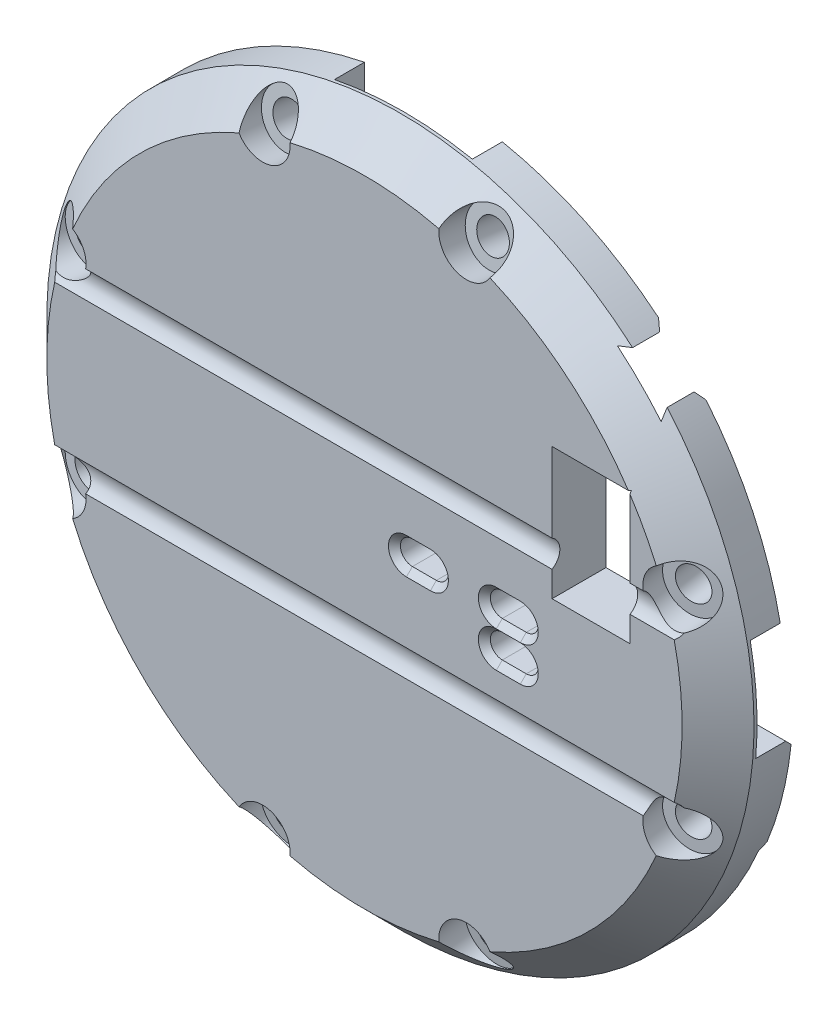
SolidWorks part; units mm, degrees
ref_plane "Front Plane" through (0, 0, 0) normal (0, 0, 1) x (1, 0, 0)
ref_plane "Top Plane" through (0, 0, 0) normal (0, 1, 0) x (1, 0, 0)
ref_plane "Right Plane" through (0, 0, 0) normal (1, 0, 0) x (0, 0, -1)
sketch "Sketch1" plane through (0, 0, 0) normal (0, 0, 1) x (1, 0, 0)
  circle A0 centre (0, 0) radius 29.5
  dimension "D1" = 59
extrude "Boss-Extrude1" add sketch "Sketch1" along normal blind 5.75
sketch "Sketch3" plane through (0, 0, 0) normal (0, 0, -1) x (-1, 0, 0)
  line L1 (-22.25, -22.25) -> (22.25, -22.25)
  line L2 (-22.25, -22.25) -> (-22.25, 22.25)
  line L3 (-22.25, 22.25) -> (22.25, 22.25)
  line L4 (22.25, -22.25) -> (22.25, 22.25)
  line L5 (-22.25, -22.25) -> (22.25, 22.25) construction
  line L6 (-22.25, 22.25) -> (22.25, -22.25) construction
  point P0 (0, 0)
  dimension "D1" = 44.5
extrude "Cut-Extrude1" cut sketch "Sketch3" against normal blind 3.25
sketch "Sketch26" plane through (0, 0, 0) normal (0, 0, -1) x (-1, 0, 0)
  line L1 (22.25, 19.3698) -> (22.25, 17.8098)
  line L2 (19.3698, -22.25) -> (17.8098, -22.25)
  line L3 (-22.25, -19.3698) -> (-22.25, -17.8098)
  line L4 (17.8098, 22.25) -> (19.3698, 22.25)
  line L6 (22.25, -17.8098) -> (22.25, -19.3698)
  line L7 (-17.8098, -22.25) -> (-19.3698, -22.25)
  arc A4 (-22.25, -19.3698) -> (-19.3698, -22.25) centre (0, 0) ccw
  arc A5 (-22.25, -17.8098) -> (-17.8098, -22.25) centre (0, 0) ccw
  arc A6 (22.25, 17.8098) -> (17.8098, 22.25) centre (0, 0) ccw
  arc A7 (22.25, 19.3698) -> (19.3698, 22.25) centre (0, 0) ccw
  arc A8 (17.8098, -22.25) -> (22.25, -17.8098) centre (0, 0) ccw
  arc A9 (19.3698, -22.25) -> (22.25, -19.3698) centre (0, 0) ccw
  dimension "D1" = 1
extrude "Boss-Extrude5" add sketch "Sketch26" against normal up to surface (3.25 mm away) up to face at (0, 0, 3.25)
chamfer "Chamfer2" distance 3 angle 45 1 edges at (29.5, 0, 5.75)
sketch "Sketch9" plane through (0, 0, 0) normal (1, 0, 0) x (0, 0, -1)
  line L0 (-26.5723, 0) -> (15.7273, 0) construction
  line L3 (-5.75, 26.5) -> (-5.75, -26.5) construction
  circle A0 centre (-6.4, 7) radius 1.3
  circle A1 centre (-6.4, -7) radius 1.3
  dimension "D1" = 2.6
  dimension "D2" = 14
  dimension "D3" = 0.65
extrude "Cut-Extrude5" cut sketch "Sketch9" against normal through all both and the other way through all
sketch "Sketch10" plane through (0, 0, 0) normal (0, 0, -1) x (-1, 0, 0)
  line L1 (22.0007, 5.75) -> (34.0342, 5.75)
  line L2 (22.0007, 5.75) -> (22.0007, -5.75)
  line L3 (22.0007, -5.75) -> (34.0342, -5.75)
  line L4 (34.0342, 5.75) -> (34.0342, -5.75)
  line L8 (-22.0007, -5.75) -> (-34.0342, -5.75)
  line L9 (-22.0007, -5.75) -> (-22.0007, 5.75)
  line L10 (-22.0007, 5.75) -> (-34.0342, 5.75)
  line L11 (-34.0342, -5.75) -> (-34.0342, 5.75)
  line L12 (-5.75, 22.0007) -> (-5.75, 34.0342)
  line L13 (-5.75, 22.0007) -> (5.75, 22.0007)
  line L14 (5.75, 22.0007) -> (5.75, 34.0342)
  line L15 (-5.75, 34.0342) -> (5.75, 34.0342)
  line L16 (5.75, -22.0007) -> (5.75, -34.0342) [skipped]
  line L17 (5.75, -22.0007) -> (-5.75, -22.0007) [skipped]
  line L18 (-5.75, -22.0007) -> (-5.75, -34.0342) [skipped]
  line L19 (5.75, -34.0342) -> (-5.75, -34.0342) [skipped]
  point P4 (22.0007, 0)
  point P21 (0, 0)
  dimension "D1" = 11.5
  dimension "D2" = 4
extrude "Cut-Extrude6" cut sketch "Sketch10" against normal blind 2.5
sketch "Sketch13" plane through (0, 0, 3.25) normal (0, 0, -1) x (-1, 0, 0)
  line L0 (-22.25, 18.5994) -> (-22.25, -17.8098) construction
  line L1 (-22.15, 14.75) -> (-15.65, 14.75)
  line L2 (-22.15, 14.75) -> (-22.15, 3.75)
  line L3 (-22.15, 3.75) -> (-15.65, 3.75)
  line L4 (-15.65, 14.75) -> (-15.65, 3.75)
  line L5 (17.8098, 22.25) -> (-18.5994, 22.25) construction
  point P23 (0, 0)
  dimension "D1" = 0.1
  dimension "D2" = 7.5
  dimension "D4" = 11
  dimension "D3" = 6.5
extrude "Cut-Extrude9" cut sketch "Sketch13" against normal through all
sketch "Sketch14" plane through (0, 0, 0) normal (0, 0, -1) x (-1, 0, 0)
  line L1 (-35.1198, 0) -> (-19.2322, 0)
  line L2 (-35.1198, 0) -> (-35.1198, -11.6)
  line L3 (-35.1198, -11.6) -> (-19.2322, -11.6)
  line L4 (-19.2322, 0) -> (-19.2322, -11.6)
  dimension "D1" = 11.6
extrude "Cut-Extrude10" cut sketch "Sketch14" against normal up to surface (2.5 mm away) up to face at (25.7335, 0, 2.5)
sketch "Sketch15" plane through (0, 0, 5.75) normal (0, 0, 1) x (1, 0, 0)
  line L0 (0, 0) -> (12.0208, 12.0208) construction
  line L1 (0, 0) -> (36.7921, 0) construction
  circle A0 centre (12.0208, 12.0208) radius 12.5
  circle A1 centre (0, 0) radius 29.5 construction
  dimension "D2" = 25
  dimension "D1" = 45
ref_axis "Axis1" through (0, 0, -0.2945) along (0, 0, 1)
ref_axis "Axis2" through (0, 31.9, 0) along (0, -1, 0)
ref_plane "Plane1" through (0, 0, 0) normal (0.1392, 0, 0.9903) x (0, -1, 0)
sketch "Sketch23" plane through (0, 0, 2.5) normal (0, 0, -1) x (-1, 0, 0)
  line L0 (-22.25, -2.55) -> (-29.3896, -2.55)
  line L1 (-22.25, -2.55) -> (-22.25, -11.6)
  line L2 (-22.25, -11.6) -> (-27.1236, -11.6)
  line L3 (-22.25, 5.75) -> (-28.9342, 5.75) construction
  arc A0 (-29.3896, -2.55) -> (-27.1236, -11.6) centre (0, 0) ccw
  arc A1 (-28.9342, 5.75) -> (-27.1236, -11.6) centre (0, 0) ccw construction
  dimension "D1" = 8.3
extrude "Boss-Extrude3" add sketch "Sketch23" along normal blind 3
sketch "Sketch17" plane through (0, 0, 0) normal (0.1392, 0, 0.9903) x (0, -1, 0)
  line L0 (0, 0) -> (0, 33.2124) construction
  line L1 (0, 0.041) -> (0, -0.8607) construction
  circle A0 centre (-8.5, 24.5) radius 1.35
  circle A1 centre (8.5, 24.5) radius 1.35
  dimension "D1" = 2.7
  dimension "D2" = 17
  dimension "D3" = 24.5
extrude "Cut-Extrude12" cut sketch "Sketch17" along normal through all
sketch "Sketch18" plane through (0, 0, 0) normal (0.1392, 0, 0.9903) x (0, -1, 0)
  circle A0 centre (-8.5, 24.5) radius 2.3
  circle A1 centre (8.5, 24.5) radius 2.3
  dimension "D1" = 4.6
extrude "Cut-Extrude13" cut sketch "Sketch18" against normal blind 13 from offset 20
pattern_circular "CirPattern1" count 4 over 360 about axis through (0, 0, -0.2945) along (0, 0, 1) of "Cut-Extrude12", "Cut-Extrude13"
sketch "Sketch19" plane through (0, 0, 5.75) normal (0, 0, 1) x (1, 0, 0)
  line L0 (3.5, 0.75) -> (5.5, 0.75) construction
  line L1 (3.5, 1.75) -> (5.5, 1.75)
  line L2 (3.5, -0.25) -> (5.5, -0.25)
  line L3 (11, 0.75) -> (13, 0.75) construction
  line L4 (11, 1.75) -> (13, 1.75)
  line L5 (11, -0.25) -> (13, -0.25)
  line L6 (11, -2.25) -> (13, -2.25) construction
  line L7 (11, -1.25) -> (13, -1.25)
  line L8 (11, -3.25) -> (13, -3.25)
  arc A0 (3.5, 1.75) -> (3.5, -0.25) centre (3.5, 0.75) ccw
  arc A1 (5.5, -0.25) -> (5.5, 1.75) centre (5.5, 0.75) ccw
  arc A2 (11, 1.75) -> (11, -0.25) centre (11, 0.75) ccw
  arc A3 (13, -0.25) -> (13, 1.75) centre (13, 0.75) ccw
  arc A4 (11, -1.25) -> (11, -3.25) centre (11, -2.25) ccw
  arc A5 (13, -3.25) -> (13, -1.25) centre (13, -2.25) ccw
  point P2 (4.5, 0.75)
  point P8 (12, 0.75)
  point P16 (12, -2.25)
  dimension "D1" = 1
  dimension "D2" = 3
  dimension "D3" = 7.5
  dimension "D4" = 4.5
  dimension "D5" = 2
  dimension "D6" = 0.75
extrude "Cut-Extrude14" cut sketch "Sketch19" against normal through all
sketch "Sketch21" plane through (0, 0, 3.25) normal (0, 0, -1) x (-1, 0, 0)
  line L61 (-5.5, -0.35) -> (-3.5, -0.35)
  line L62 (-3.5, 1.85) -> (-5.5, 1.85)
  line L63 (-5.5, -0.35) -> (-3.5, -0.35)
  line L64 (-3.5, 1.85) -> (-5.5, 1.85)
  line L69 (-11, 1.85) -> (-13, 1.85)
  line L70 (-13, -0.35) -> (-11, -0.35)
  line L71 (-11, 1.85) -> (-13, 1.85)
  line L72 (-13, -0.35) -> (-11, -0.35)
  line L75 (-5.5, -1.35) -> (-3.5, -1.35)
  line L76 (-3.5, 2.85) -> (-5.5, 2.85)
  line L77 (-11, -1.15) -> (-13, -1.15)
  line L78 (-13, -3.35) -> (-11, -3.35)
  line L79 (-11, -1.15) -> (-13, -1.15)
  line L80 (-13, -3.35) -> (-11, -3.35)
  line L81 (-11, 2.85) -> (-13, 2.85)
  line L84 (-13, -4.35) -> (-11, -4.35)
  line L85 (-13, -1.35) -> (-11, -1.35) construction
  line L86 (-11, -0.15) -> (-13, -0.15) construction
  arc A55 (-5.5, 1.85) -> (-5.5, -0.35) centre (-5.5, 0.75) ccw
  arc A56 (-3.5, -0.35) -> (-3.5, 1.85) centre (-3.5, 0.75) ccw
  arc A57 (-5.5, 1.85) -> (-5.5, -0.35) centre (-5.5, 0.75) ccw
  arc A58 (-3.5, -0.35) -> (-3.5, 1.85) centre (-3.5, 0.75) ccw
  arc A65 (-13, 1.85) -> (-13, -0.35) centre (-13, 0.75) ccw
  arc A66 (-11, -0.35) -> (-11, 1.85) centre (-11, 0.75) ccw
  arc A67 (-13, 1.85) -> (-13, -0.35) centre (-13, 0.75) ccw
  arc A68 (-11, -0.35) -> (-11, 1.85) centre (-11, 0.75) ccw
  arc A73 (-5.5, 2.85) -> (-5.5, -1.35) centre (-5.5, 0.75) ccw
  arc A74 (-3.5, -1.35) -> (-3.5, 2.85) centre (-3.5, 0.75) ccw
  arc A75 (-13, -1.15) -> (-13, -3.35) centre (-13, -2.25) ccw
  arc A76 (-11, -3.35) -> (-11, -1.15) centre (-11, -2.25) ccw
  arc A77 (-13, -1.15) -> (-13, -3.35) centre (-13, -2.25) ccw
  arc A78 (-11, -3.35) -> (-11, -1.15) centre (-11, -2.25) ccw
  arc A80 (-13, 2.85) -> (-14.4697, -0.75) centre (-13, 0.75) ccw
  arc A81 (-11, -4.35) -> (-9.5303, -0.75) centre (-11, -2.25) ccw
  arc A84 (-9.5303, -0.75) -> (-11, 2.85) centre (-11, 0.75) ccw
  arc A85 (-11, -4.35) -> (-11, -0.15) centre (-11, -2.25) ccw construction
  arc A86 (-14.4697, -0.75) -> (-13, -4.35) centre (-13, -2.25) ccw
  arc A87 (-11, -1.35) -> (-11, 2.85) centre (-11, 0.75) ccw construction
  arc A88 (-13, 2.85) -> (-13, -1.35) centre (-13, 0.75) ccw construction
  arc A90 (-13, -0.15) -> (-13, -4.35) centre (-13, -2.25) ccw construction
  dimension "D1" = 0.1
  dimension "D2" = 0.1
  dimension "D3" = 0.1
  dimension "D4" = 1
  dimension "D5" = 1
extrude "Boss-Extrude2" add sketch "Sketch21" along normal blind 2
fillet "Fillet1" radius 1 7 edges at (7.6, 0.75, 3.25) (4.5, 2.85, 3.25) (1.4, 0.75, 3.25) (14.9442, -3.0437, 3.25) (9.0558, -3.0437, 3.25) (4.5, -1.35, 3.25) (12, -4.35, 3.25)
sketch "Sketch25" plane through (0, 0, 3.25) normal (0, 0, -1) x (-1, 0, 0)
  line L0 (-22.25, 15.75) -> (-22.25, 14.75)
  line L1 (-22.25, 5.75) -> (-22.25, 19.3698) construction
  line L2 (-22.25, 14.75) -> (-15.65, 14.75)
  line L3 (-15.65, 14.75) -> (-15.65, 3.75)
  line L4 (-15.65, 3.75) -> (-22.25, 3.75)
  line L5 (-22.25, -2.55) -> (-22.25, 5.75) construction
  line L6 (-22.25, 3.75) -> (-22.25, 2.75)
  line L7 (-22.25, 2.75) -> (-14.65, 2.75)
  line L8 (-14.65, 2.75) -> (-14.65, 15.75)
  line L9 (-14.65, 15.75) -> (-22.25, 15.75)
  dimension "D1" = 1
  dimension "D2" = 1
  dimension "D3" = 1
extrude "Boss-Extrude4" add sketch "Sketch25" along normal blind 2
chamfer "Chamfer3" distance 0.5 angle 45 3 edges at (18.45, 15.75, 1.25) (18.45, 2.75, 1.25) (14.65, 9.25, 1.25)
chamfer "Chamfer4" distance 0.5 angle 45 12 edges at (10, 0.75, 5.75) (12, -0.25, 5.75) (12, 1.75, 5.75) (14, 0.75, 5.75) (12, -3.25, 5.75) (14, -2.25, 5.75) (10, -2.25, 5.75) (12, -1.25, 5.75) (2.5, 0.75, 5.75) (4.5, -0.25, 5.75) (4.5, 1.75, 5.75) (6.5, 0.75, 5.75)
chamfer "Chamfer5" distance 0.5 angle 45 9 edges at (-22.25, 11.7799, 0) (-22.25, -11.7799, 0) (0, -22.25, 0) (22.25, -7.075, -0.5) (22.25, 12.5599, 0) (-11.7799, 22.25, 0) (12.5599, 22.25, 0) (24.6868, -11.6, -0.5) (25.8198, -2.55, -0.5)
